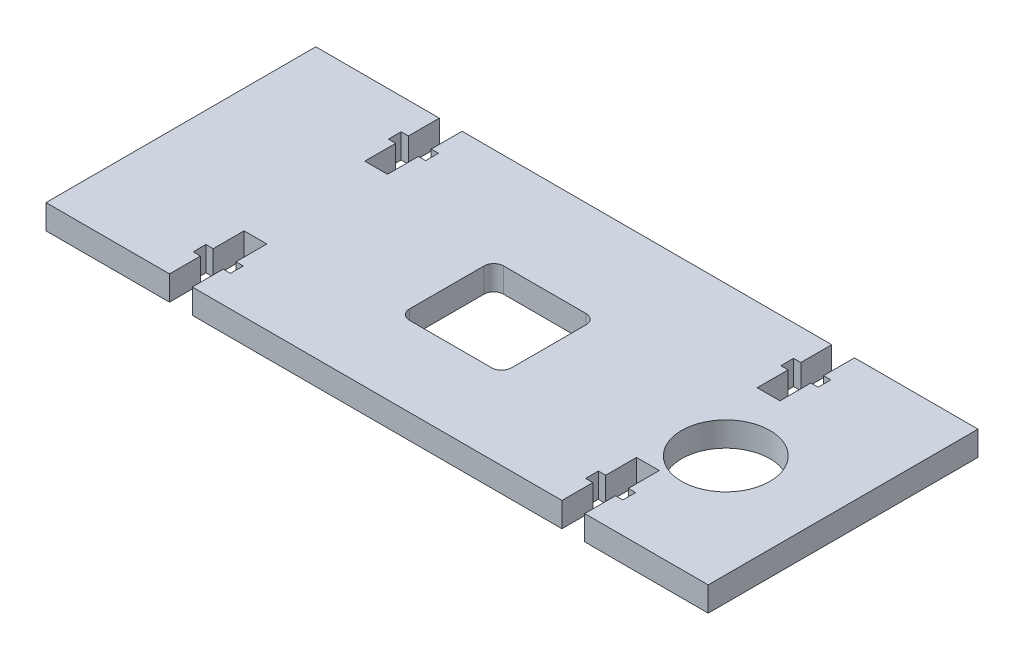
SolidWorks part; units mm, degrees
ref_plane "Front Plane" through (0, 0, 0) normal (0, 0, 1) x (1, 0, 0)
ref_plane "Top Plane" through (0, 0, 0) normal (0, 1, 0) x (1, 0, 0)
ref_plane "Right Plane" through (0, 0, 0) normal (1, 0, 0) x (0, 0, -1)
sketch "Sketch1" plane through (0, 0, 0) normal (0, 1, 0) x (1, 0, 0)
  line L1 (-42.8625, -17.4625) -> (42.8625, -17.4625)
  line L2 (-42.8625, -17.4625) -> (-42.8625, 17.4625)
  line L3 (-42.8625, 17.4625) -> (42.8625, 17.4625)
  line L4 (42.8625, -17.4625) -> (42.8625, 17.4625)
  line L5 (-42.8625, -17.4625) -> (42.8625, 17.4625) construction
  line L6 (-42.8625, 17.4625) -> (42.8625, -17.4625) construction
  point P0 (0, 0)
  dimension "D1" = 85.725
  dimension "D2" = 34.925
extrude "Boss-Extrude1" add sketch "Sketch1" along normal blind 3.175
sketch "Sketch2" plane through (0, 0, 0) normal (0, -1, 0) x (-1, 0, 0)
  line L0 (3.3881, -2.4141) -> (-1.7731, 0.3271) construction
  line L2 (7.4115, 5.0525) -> (-5.7965, 5.0525)
  line L3 (7.4115, 5.0525) -> (7.4115, -7.1395)
  line L4 (7.4115, -7.1395) -> (-5.7965, -7.1395)
  line L5 (-5.7965, 5.0525) -> (-5.7965, -7.1395)
  line L6 (7.4115, 5.0525) -> (-5.7965, -7.1395) construction
  line L7 (7.4115, -7.1395) -> (-5.7965, 5.0525) construction
  circle A0 centre (-29.5375, -1.8635) radius 5.715
  point P4 (0.8075, -1.0435)
  dimension "D3" = 11.43
  dimension "D1" = 13.208
  dimension "D2" = 12.192
extrude "Cut-Extrude1" cut sketch "Sketch2" against normal through all
fillet "Fillet1" radius 1.27 4 edges at (5.7965, 1.5875, -5.0525) (-7.4115, 1.5875, -5.0525) (5.7965, 1.5875, 7.1395) (-7.4115, 1.5875, 7.1395)
sketch "Sketch3" plane through (0, 0, 0) normal (0, -1, 0) x (1, 0, 0)
  line L0 (-42.8625, 17.4625) -> (42.8625, 17.4625) construction
  line L1 (-26.8732, 17.4625) -> (-23.9268, 17.4625)
  line L2 (-26.8732, 17.4625) -> (-26.8732, 13.462)
  line L3 (-26.8732, 7.8105) -> (-23.9268, 7.8105)
  line L4 (-23.9268, 17.4625) -> (-23.9268, 13.462)
  line L5 (-26.8732, 17.4625) -> (-23.9268, 7.8105) construction
  line L6 (-26.8732, 13.462) -> (-27.813, 13.462)
  line L7 (-22.987, 11.811) -> (-23.9268, 11.811)
  line L8 (-22.987, 11.811) -> (-22.987, 13.462)
  line L9 (-22.987, 13.462) -> (-23.9268, 13.462)
  line L10 (-27.813, 11.811) -> (-27.813, 13.462)
  line L11 (-22.987, 11.811) -> (-27.813, 13.462) construction
  line L12 (-22.987, 13.462) -> (-27.813, 11.811) construction
  line L13 (-23.9268, 11.811) -> (-23.9268, 7.8105)
  line L14 (-26.8732, 11.811) -> (-27.813, 11.811)
  line L15 (-26.8732, 11.811) -> (-26.8732, 7.8105)
  line L16 (-25.4, 7.8105) -> (-25.4, 17.4625) construction
  line L17 (0, 17.4625) -> (0, -17.4625) construction
  line L18 (42.8625, -17.4625) -> (-42.8625, -17.4625) construction
  line L19 (25.4, 7.8105) -> (25.4, 17.4625) construction
  line L20 (22.987, 13.462) -> (27.813, 11.811) construction
  line L21 (22.987, 11.811) -> (27.813, 13.462) construction
  line L22 (26.8732, 17.4625) -> (23.9268, 7.8105) construction
  line L23 (26.8732, 11.811) -> (26.8732, 7.8105)
  line L24 (26.8732, 11.811) -> (27.813, 11.811)
  line L25 (23.9268, 11.811) -> (23.9268, 7.8105)
  line L26 (27.813, 11.811) -> (27.813, 13.462)
  line L27 (22.987, 13.462) -> (23.9268, 13.462)
  line L28 (22.987, 11.811) -> (22.987, 13.462)
  line L29 (22.987, 11.811) -> (23.9268, 11.811)
  line L30 (26.8732, 13.462) -> (27.813, 13.462)
  line L31 (23.9268, 17.4625) -> (23.9268, 13.462)
  line L32 (26.8732, 7.8105) -> (23.9268, 7.8105)
  line L33 (26.8732, 17.4625) -> (26.8732, 13.462)
  line L34 (26.8732, 17.4625) -> (23.9268, 17.4625)
  line L35 (-42.8625, 0) -> (-37.7203, 0) construction
  line L36 (-42.8625, -17.4625) -> (-42.8625, 17.4625) construction
  line L37 (26.8732, -17.4625) -> (23.9268, -7.8105) construction
  line L38 (22.987, -11.811) -> (27.813, -13.462) construction
  line L39 (22.987, -13.462) -> (27.813, -11.811) construction
  line L40 (25.4, -7.8105) -> (25.4, -17.4625) construction
  line L41 (26.8732, -17.4625) -> (23.9268, -17.4625)
  line L42 (26.8732, -17.4625) -> (26.8732, -13.462)
  line L43 (26.8732, -7.8105) -> (23.9268, -7.8105)
  line L44 (23.9268, -17.4625) -> (23.9268, -13.462)
  line L45 (26.8732, -13.462) -> (27.813, -13.462)
  line L46 (22.987, -11.811) -> (23.9268, -11.811)
  line L47 (22.987, -11.811) -> (22.987, -13.462)
  line L48 (22.987, -13.462) -> (23.9268, -13.462)
  line L49 (27.813, -11.811) -> (27.813, -13.462)
  line L50 (23.9268, -11.811) -> (23.9268, -7.8105)
  line L51 (26.8732, -11.811) -> (27.813, -11.811)
  line L52 (26.8732, -11.811) -> (26.8732, -7.8105)
  line L53 (-25.4, -7.8105) -> (-25.4, -17.4625) construction
  line L54 (-22.987, -13.462) -> (-27.813, -11.811) construction
  line L55 (-22.987, -11.811) -> (-27.813, -13.462) construction
  line L56 (-26.8732, -17.4625) -> (-23.9268, -7.8105) construction
  line L57 (-26.8732, -11.811) -> (-26.8732, -7.8105)
  line L58 (-26.8732, -11.811) -> (-27.813, -11.811)
  line L59 (-23.9268, -11.811) -> (-23.9268, -7.8105)
  line L60 (-27.813, -11.811) -> (-27.813, -13.462)
  line L61 (-22.987, -13.462) -> (-23.9268, -13.462)
  line L62 (-22.987, -11.811) -> (-22.987, -13.462)
  line L63 (-22.987, -11.811) -> (-23.9268, -11.811)
  line L64 (-26.8732, -13.462) -> (-27.813, -13.462)
  line L65 (-23.9268, -17.4625) -> (-23.9268, -13.462)
  line L66 (-26.8732, -7.8105) -> (-23.9268, -7.8105)
  line L67 (-26.8732, -17.4625) -> (-26.8732, -13.462)
  line L68 (-26.8732, -17.4625) -> (-23.9268, -17.4625)
  point P6 (-25.4, 12.6365)
  point P18 (-25.4, 12.6365)
  point P36 (25.4, 12.6365)
  point P56 (25.4, -12.6365)
  point P71 (-25.4, -12.6365)
  dimension "D1" = 9.652
  dimension "D2" = 2.9464
  dimension "D3" = 1.651
  dimension "D4" = 4.826
  dimension "D5" = 25.4
extrude "Cut-Extrude2" cut sketch "Sketch3" against normal through all
